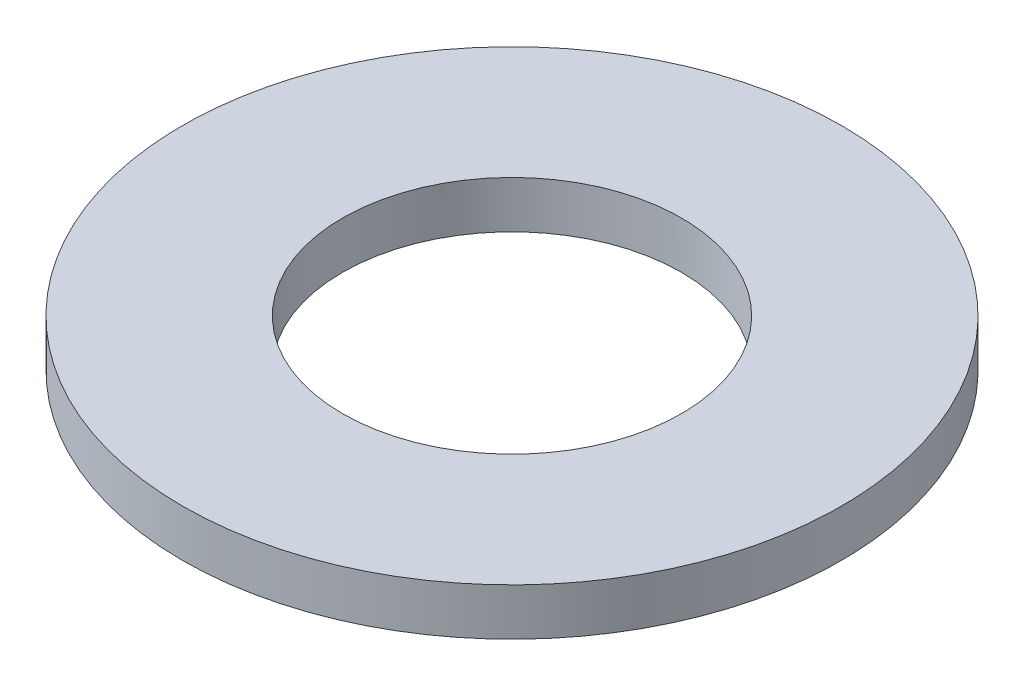
SolidWorks part; units mm, degrees
ref_plane "Front Plane" through (0, 0, 0) normal (0, 0, 1) x (1, 0, 0)
ref_plane "Top Plane" through (0, 0, 0) normal (0, 1, 0) x (1, 0, 0)
ref_plane "Right Plane" through (0, 0, 0) normal (1, 0, 0) x (0, 0, -1)
sketch "Sketch1" plane through (0, 0, 0) normal (0, 1, 0) x (1, 0, 0)
  circle A0 centre (0, 0) radius 1750
extrude "Boss-Extrude1" add sketch "Sketch1" along normal blind 500
sketch "Sketch2" plane through (0, 500, 0) normal (0, 1, 0) x (1, 0, 0)
  circle A0 centre (0, 0) radius 900
extrude "Cut-Extrude2" cut sketch "Sketch2" against normal blind 300
sketch "Sketch3" plane through (0, 0, 0) normal (0, -1, 0) x (1, 0, 0)
  circle A0 centre (0, 0) radius 600
extrude "Cut-Extrude3" cut sketch "Sketch3" against normal blind 300
sketch "Sketch4" plane through (0, 0, 0) normal (0, -1, 0) x (-1, 0, 0)
  circle A0 centre (0, 0) radius 950
  circle A1 centre (0, 0) radius 1700
extrude "Cut-Extrude5" cut sketch "Sketch4" against normal blind 490
sketch "Sketch5" plane through (0, 0, 0) normal (0, 0, 1) x (1, 0, 0)
  line L0 (0, 0) -> (0, 250)
  line L1 (0, 250) -> (1750, 250)
  line L2 (1750, 0) -> (1750, 500) construction
  line L3 (1750, 250) -> (1750, 0)
  line L4 (1750, 0) -> (-1750, 0)
  line L5 (-1750, 0) -> (-1750, 250)
  line L6 (-1750, 500) -> (-1750, 0) construction
  line L7 (-1750, 250) -> (0, 250)
extrude "Cut-Extrude6" cut sketch "Sketch5" against normal through all both and the other way through all contours L7 L5 L4 L0 | L4 L3 L1 L0 region at (-875, 125, 0) region at (875, 125, 0)
